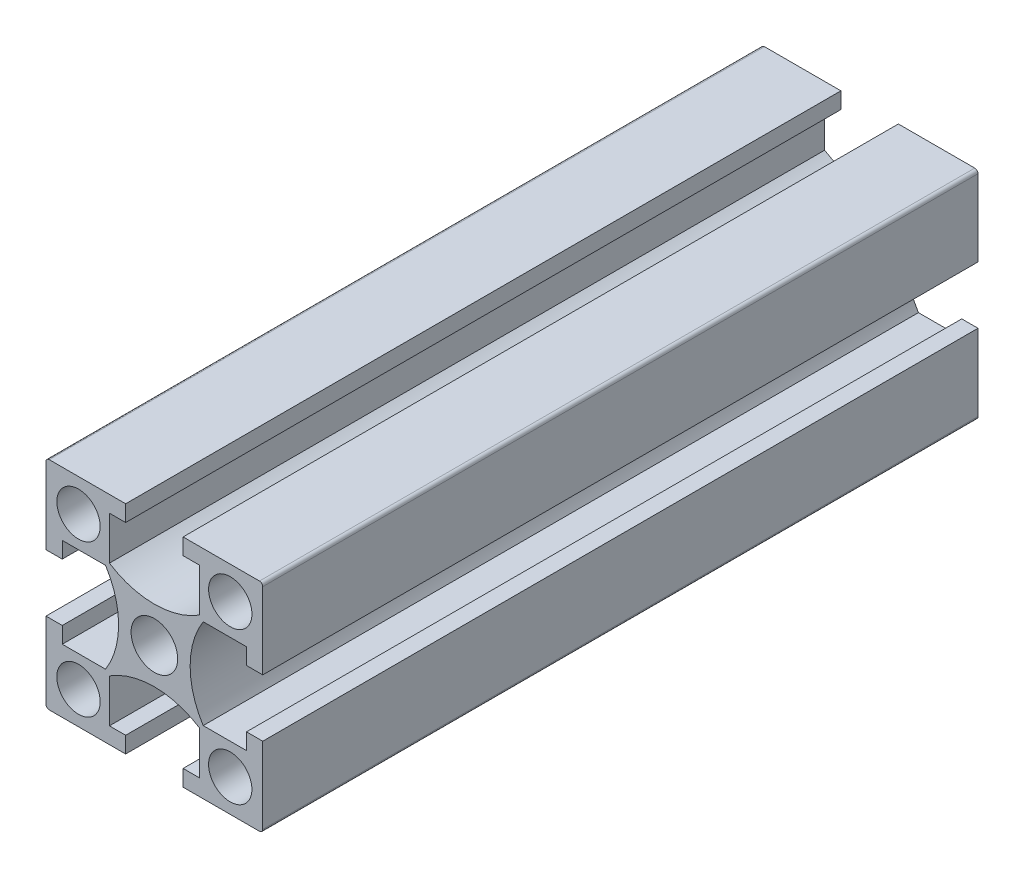
SolidWorks part; units mm, degrees
ref_plane "정면" through (0, 0, 0) normal (0, 0, 1) x (1, 0, 0)
ref_plane "윗면" through (0, 0, 0) normal (0, 1, 0) x (1, 0, 0)
ref_plane "우측면" through (0, 0, 0) normal (1, 0, 0) x (0, 0, -1)
sketch "스케치1" plane through (0, 0, 0) normal (0, 0, 1) x (1, 0, 0)
  line L0 (0, 32.0265) -> (0, -31.6588) construction
  line L1 (-10, 10) -> (-10, -10)
  line L2 (-10, 10) -> (10, 10)
  line L3 (-10, 2.65) -> (-8.5, 2.65)
  line L4 (13.6618, 0) -> (-11.6993, 0) construction
  line L5 (-8.5, 2.65) -> (-8.5, 4.15)
  line L6 (-8.5, 4.15) -> (-4.5032, 4.15)
  line L7 (-10, -2.65) -> (-8.5, -2.65)
  line L8 (-8.5, -2.65) -> (-8.5, -4.15)
  line L9 (-8.5, -4.15) -> (-4.5032, -4.15)
  line L10 (-10, -10) -> (10, -10)
  line L11 (10, 10) -> (10, -10)
  circle A0 centre (-7, 7) radius 2
  circle A1 centre (-7, -7) radius 2
  arc A2 (-4.5032, 4.15) -> (-4.5032, -4.15) centre (-11.0587, 0) cw
  circle A3 centre (0, 0) radius 2.15
  circle A4 centre (7, 7) radius 2
  circle A5 centre (7, -7) radius 2
  point P21 (-10, 0)
  point P23 (-3.3, 0)
  point P31 (0, -10)
  point P32 (0, 10)
  dimension "D3" = 4
  dimension "D9" = 6.7
  dimension "D10" = 4.3
  dimension "D11" = 7.7587
  dimension "D1" = 20
  dimension "D2" = 20
  dimension "D4" = 14
  dimension "D5" = 14
  dimension "D6" = 5.3
  dimension "D7" = 8.3
  dimension "D8" = 1.5
extrude "보스-돌출1" add sketch "스케치1" along normal blind 66 contours A0 | A4 | A3 | A5 | A1 | A2 L6 L5 L3 L1 L7 L8 L9 | L2 L11 L10 L1 region at (-6.6069, 0, 0) region at (-7, 7, 0) region at (-7, -7, 0) region at (0, 0, 0) region at (7, 7, 0) region at (7, -7, 0)
extrude "컷-돌출1" cut sketch "스케치1<3>" along normal up to next contours A2 L6 L5 L3 L1 L7 L8 L9 region at (-6.6069, 0, 0)
sketch "스케치1<3>" plane through (0, 0, 0) normal (0, 0, 1) x (1, 0, 0) same geometry as "스케치1"
pattern_circular "원형 패턴1" count 4 over 360 about axis through (0, 0, 66) along (0, 0, -1) of "컷-돌출1" reverse direction yes
fillet "필렛1" radius 0.3 4 edges at (10, -10, 33) (-10, -10, 33) (-10, 10, 33) (10, 10, 33)
